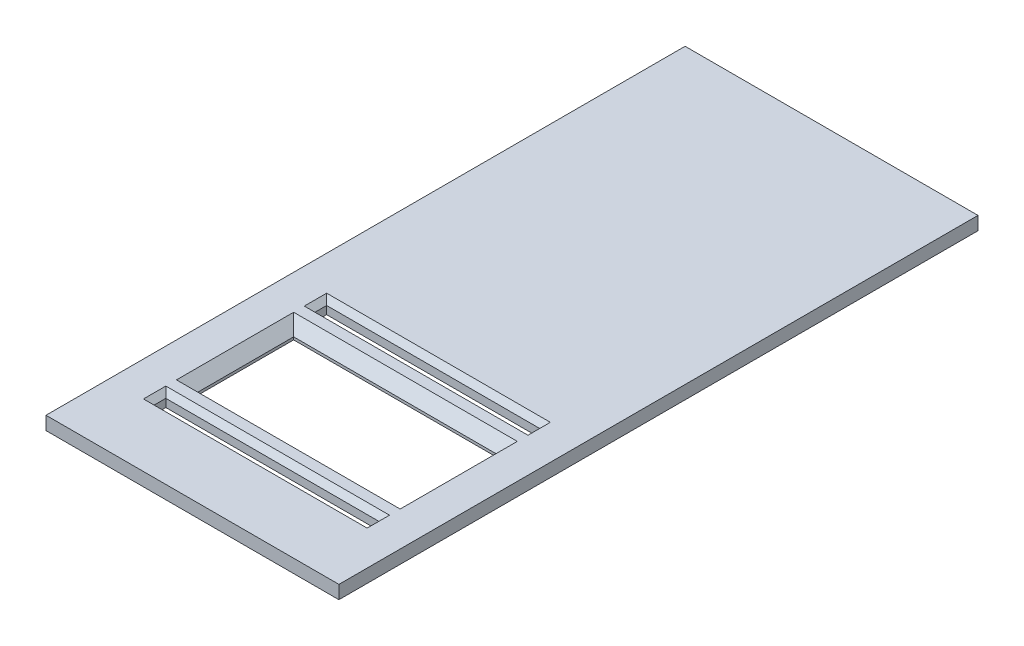
SolidWorks part; units mm, degrees
ref_plane "Front Plane" through (0, 0, 0) normal (0, 0, 1) x (1, 0, 0)
ref_plane "Top Plane" through (0, 0, 0) normal (0, 1, 0) x (1, 0, 0)
ref_plane "Right Plane" through (0, 0, 0) normal (1, 0, 0) x (0, 0, -1)
sketch "Sketch1" plane through (0, 0, 0) normal (0, 1, 0) x (1, 0, 0)
  line L1 (-69.85, -50.8) -> (69.85, -50.8)
  line L2 (-69.85, -50.8) -> (-69.85, 254)
  line L3 (-69.85, 254) -> (69.85, 254)
  line L4 (69.85, -50.8) -> (69.85, 254)
  line L5 (0, 254) -> (0, -50.8) construction
  line L6 (-69.85, 101.6) -> (69.85, 101.6) construction
  point P0 (0, 101.6)
  dimension "D1" = 304.8
  dimension "D2" = 139.7
  dimension "D3" = 101.6
extrude "Boss-Extrude1" add sketch "Sketch1" along normal blind 6.35
sketch "Sketch2" plane through (0, 6.35, 0) normal (0, 1, 0) x (1, 0, 0)
  line L0 (-69.85, -50.8) -> (69.85, -50.8) construction
  line L1 (-48.26, 0) -> (48.26, 0)
  line L2 (-48.26, 0) -> (-48.26, 45.72)
  line L3 (-48.26, 45.72) -> (48.26, 45.72)
  line L4 (48.26, 0) -> (48.26, 45.72)
  line L5 (0, 45.72) -> (0, 0) construction
  line L6 (-48.26, 22.86) -> (48.26, 22.86) construction
  point P0 (0, 22.86)
  dimension "D1" = 45.72
  dimension "D2" = 96.52
  dimension "D3" = 50.8
extrude "Main Hole" cut sketch "Sketch2" against normal through all
ref_plane "Plane1" through (0, 0, -22.86) normal (0, 0, 1) x (1, 0, 0)
sketch "Sketch3" plane through (0, 6.35, 0) normal (0, 1, 0) x (1, 0, 0)
  line L0 (48.26, 45.72) -> (-48.26, 45.72) construction
  line L1 (-50.8, 58.42) -> (50.8, 58.42)
  line L2 (-50.8, 58.42) -> (-50.8, 64.008)
  line L3 (-50.8, 64.008) -> (50.8, 64.008)
  line L4 (50.8, 58.42) -> (50.8, 64.008)
  point P4 (0, 58.42)
  dimension "D1" = 101.6
  dimension "D2" = 5.588
  dimension "D3" = 12.7
extrude "NeoPixel" cut sketch "Sketch3" against normal through all
mirror "Mirror2" about plane through (0, 0, -22.86) normal (0, 0, 1) of "NeoPixel"
sketch "Sketch5" plane through (0, 0, 0) normal (0, -1, 0) x (1, 0, 0)
  line L0 (69.85, -254) -> (-69.85, -254) construction
  line L1 (67.31, -251.46) -> (-67.31, -251.46)
  line L2 (67.31, -251.46) -> (67.31, 48.26)
  line L3 (67.31, 48.26) -> (-67.31, 48.26)
  line L4 (-67.31, -251.46) -> (-67.31, 48.26)
  line L5 (64.77, -248.92) -> (-64.77, -248.92)
  line L6 (64.77, -248.92) -> (64.77, 45.72)
  line L7 (64.77, 45.72) -> (-64.77, 45.72)
  line L8 (-64.77, -248.92) -> (-64.77, 45.72)
  line L9 (-69.85, -254) -> (-69.85, 50.8) construction
  line L10 (-69.85, 50.8) -> (69.85, 50.8) construction
  line L11 (69.85, 50.8) -> (69.85, -254) construction
  dimension "D1" = 2.54
  dimension "D2" = 2.54
  dimension "D3" = 2.54
  dimension "D4" = 2.54
  dimension "D5" = 2.54
  dimension "D6" = 2.54
  dimension "D7" = 2.54
  dimension "D8" = 2.54
extrude "Boss-Extrude2" add sketch "Sketch5" along normal blind 2.54 contours L4 L1 L2 L3 L5 L8 L7 L6 region at (0, 0, -251.1314)
chamfer "Chamfer1" distance 2.54 angle 45 8 edges at (50.8, 6.35, 15.494) (0, 6.35, 18.288) (-50.8, 6.35, 15.494) (0, 6.35, 12.7) (-50.8, 6.35, -61.214) (0, 6.35, -58.42) (50.8, 6.35, -61.214) (0, 6.35, -64.008)
chamfer "Chamfer2" distance 5.08 angle 45 4 edges at (48.26, 6.35, -22.86) (0, 6.35, 0) (-48.26, 6.35, -22.86) (0, 6.35, -45.72)
sketch "Sketch6" plane through (0, 0, 0) normal (0, -1, 0) x (1, 0, 0)
  line L0 (0.6985, -22.86) -> (-0.6985, -22.86) construction
  line L1 (50.8, 2.54) -> (-50.8, 2.54)
  line L2 (50.8, 2.54) -> (50.8, -48.26)
  line L3 (50.8, -48.26) -> (-50.8, -48.26)
  line L4 (-50.8, 2.54) -> (-50.8, -48.26)
  line L5 (0, -48.26) -> (0, 2.54) construction
  line L6 (50.8, -22.86) -> (-50.8, -22.86) construction
  line L7 (0, -5.7277) -> (0, 5.7277) construction
  line L8 (6.35, -50.8) -> (6.35, -48.26)
  line L9 (53.34, 5.08) -> (-53.34, 5.08)
  line L10 (53.34, 5.08) -> (53.34, -50.8)
  line L11 (53.34, -50.8) -> (-53.34, -50.8)
  line L12 (-53.34, 5.08) -> (-53.34, -50.8)
  line L13 (0, -50.8) -> (0, 5.08) construction
  line L14 (53.34, -22.86) -> (-53.34, -22.86) construction
  line L31 (-6.35, -50.8) -> (-6.35, -48.26)
  line L32 (6.35, -49.53) -> (-6.35, -49.53) construction
  point P0 (0, -22.86)
  point P8 (0, -22.86)
  point P16 (0, -49.53)
  dimension "D1" = 2.54
  dimension "D2" = 2.54
  dimension "D3" = 50.8
  dimension "D4" = 101.6
  dimension "D5" = 12.7
extrude "Boss-Extrude3" [suppressed] add sketch "Sketch6" along normal blind 4.064 contours L9 L12 L11 L10 L4 L1 L2 L3
equation "\"D1@Sketch2\"=1.8in"
equation "\"D2@Sketch2\"=3.8in"
